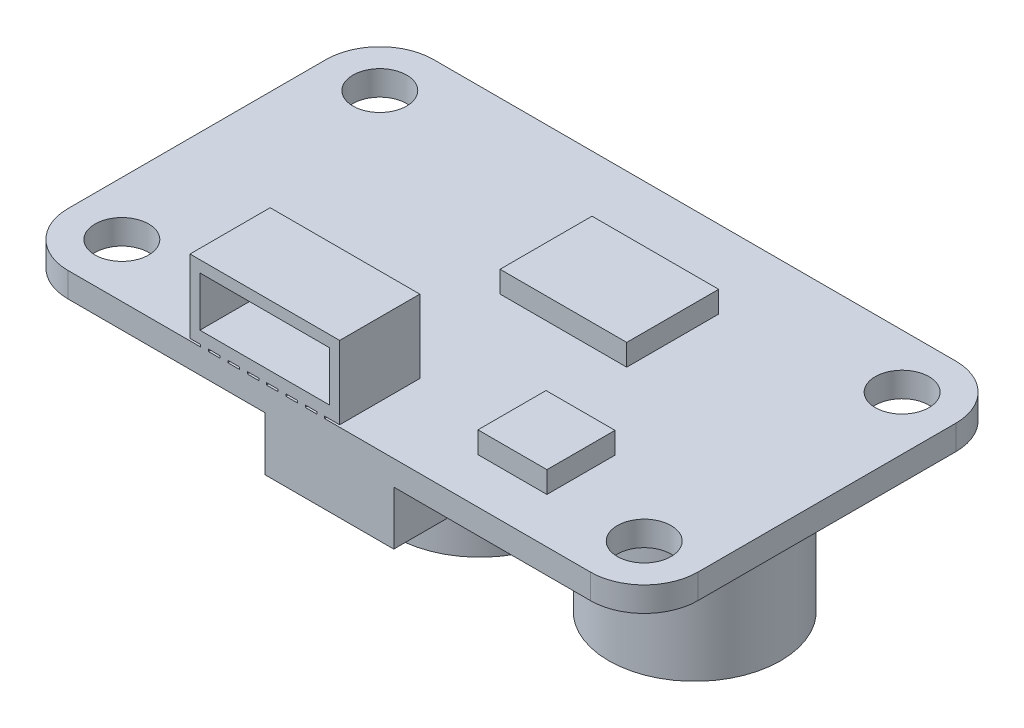
SolidWorks part; units mm, degrees
ref_plane "Front Plane" through (0, 0, 0) normal (0, 0, 1) x (1, 0, 0)
ref_plane "Top Plane" through (0, 0, 0) normal (0, 1, 0) x (1, 0, 0)
ref_plane "Right Plane" through (0, 0, 0) normal (1, 0, 0) x (0, 0, -1)
sketch "Sketch1" plane through (0, 0, 0) normal (0, 1, 0) x (1, 0, 0)
  line L0 (0, 0) -> (0, 8.5) construction
  line L1 (-14.65, 8.5) -> (14.65, 8.5)
  line L2 (-14.65, 8.5) -> (-14.65, -8.5)
  line L3 (-14.65, -8.5) -> (14.65, -8.5)
  line L4 (14.65, 8.5) -> (14.65, -8.5)
  line L5 (-14.65, 8.5) -> (14.65, -8.5) construction
  line L6 (-14.65, -8.5) -> (14.65, 8.5) construction
  line L7 (0, 8.5) -> (0, 0) construction
  line L8 (0, 0) -> (14.65, 0) construction
  circle A0 centre (-12.15, 6) radius 1.25
  circle A1 centre (-12.15, -6) radius 1.25
  circle A2 centre (12.15, -6) radius 1.25
  circle A3 centre (12.15, 6) radius 1.25
  point P0 (0, 0)
  dimension "D7" = 2.5
  dimension "D1" = 29.3
  dimension "D2" = 17
  dimension "D3" = 6
  dimension "D4" = 6
  dimension "D5" = 12.15
  dimension "D6" = 12.15
extrude "Boss-Extrude1" add sketch "Sketch1" along normal blind 1.15
fillet "Fillet1" radius 2.5 4 edges at (-14.65, 0.575, -8.5) (-14.65, 0.575, 8.5) (14.65, 0.575, -8.5) (14.65, 0.575, 8.5)
sketch "Sketch2" plane through (0, 1.15, 0) normal (0, 1, 0) x (1, 0, 0)
  line L0 (-12.15, -8.5) -> (12.15, -8.5) construction
  line L1 (-6.48, -4.7708) -> (0.4823, -4.7708)
  line L2 (-6.48, -4.7708) -> (-6.48, -8.5)
  line L3 (-6.48, -8.5) -> (0.4823, -8.5)
  line L4 (0.4823, -4.7708) -> (0.4823, -8.5)
extrude "Boss-Extrude2" add sketch "Sketch2" along normal blind 3.5
sketch "Sketch3" plane through (0, 0, 8.5) normal (0, 0, 1) x (1, 0, 0)
  line L0 (0.4823, 4.65) -> (0.4823, 1.15) construction
  line L1 (-6.48, 1.15) -> (0.4823, 1.15)
  line L2 (-6.48, 1.15) -> (-6.48, 1.25)
  line L3 (-6.48, 1.25) -> (0.4823, 1.25)
  line L4 (0.4823, 1.15) -> (0.4823, 1.25)
  line L5 (-4.7161, 1.25) -> (-4.7161, 1.15)
  line L6 (-5.9806, 1.25) -> (-5.6161, 1.25)
  line L7 (-5.9806, 1.25) -> (-5.9806, 1.15)
  line L8 (-5.9806, 1.15) -> (-5.6161, 1.15)
  line L9 (-5.6161, 1.25) -> (-5.6161, 1.15)
  line L10 (-5.0806, 1.25) -> (-5.0806, 1.15)
  line L11 (-3.8161, 1.25) -> (-3.8161, 1.15)
  line L12 (-4.1806, 1.25) -> (-4.1806, 1.15)
  line L13 (-2.9161, 1.25) -> (-2.9161, 1.15)
  line L14 (-3.2806, 1.25) -> (-3.2806, 1.15)
  line L15 (-2.0161, 1.25) -> (-2.0161, 1.15)
  line L16 (-2.3806, 1.25) -> (-2.3806, 1.15)
  line L17 (-1.1161, 1.25) -> (-1.1161, 1.15)
  line L18 (-1.4806, 1.25) -> (-1.4806, 1.15)
  line L19 (-0.2161, 1.25) -> (-0.2161, 1.15)
  line L20 (-0.5806, 1.25) -> (-0.5806, 1.15)
  line M7 (0.4823, 1.15) -> (0.4823, 4.65)
  line M9 (-6.48, 4.65) -> (-6.48, 1.15)
  dimension "D1" = 0.1
  dimension "D2" = 7
extrude "Cut-Extrude1" cut sketch "Sketch3" against normal blind 5.5 contours L7 L3 L1 M9 | L10 L3 L9 L1 | L12 L3 L5 L1 | L14 L3 L11 L1 | L16 L3 L13 L1 | L18 L3 L15 L1 | L20 L3 L17 L1 | L3 L19 L1 M7 region at (-6.2303, 1.2, 8.5) region at (-5.3484, 1.2, 8.5) region at (-4.4484, 1.2, 8.5) region at (-3.5484, 1.2, 8.5) region at (-2.6484, 1.2, 8.5) region at (-1.7484, 1.2, 8.5) region at (-0.8484, 1.2, 8.5) region at (0.1331, 1.2, 8.5)
sketch "Sketch4" plane through (0, 0, 8.5) normal (0, 0, 1) x (1, 0, 0)
  line L1 (-6.0186, 4.118) -> (0, 4.118)
  line L2 (-6.0186, 4.118) -> (-6.0186, 1.8112)
  line L3 (-6.0186, 1.8112) -> (0, 1.8112)
  line L4 (0, 4.118) -> (0, 1.8112)
extrude "Cut-Extrude2" cut sketch "Sketch4" against normal blind 3.5
sketch "Sketch5" plane through (0, 1.15, 0) normal (0, 1, 0) x (1, 0, 0)
  line L1 (-1.1534, 4.8757) -> (4.7394, 4.8757)
  line L2 (-1.1534, 4.8757) -> (-1.1534, 0.5977)
  line L3 (-1.1534, 0.5977) -> (4.7394, 0.5977)
  line L4 (4.7394, 4.8757) -> (4.7394, 0.5977)
extrude "Boss-Extrude3" add sketch "Sketch5" along normal blind 1
sketch "Sketch6" plane through (0, 1.15, 0) normal (0, 1, 0) x (1, 0, 0)
  line L1 (4.8023, -3.219) -> (8.0108, -3.219)
  line L2 (4.8023, -3.219) -> (4.8023, -6.3856)
  line L3 (4.8023, -6.3856) -> (8.0108, -6.3856)
  line L4 (8.0108, -3.219) -> (8.0108, -6.3856)
extrude "Boss-Extrude4" add sketch "Sketch6" along normal blind 1
sketch "Sketch7" plane through (0, 0, 0) normal (0, -1, 0) x (1, 0, 0)
  line L0 (0, 8.5) -> (0, -8.5) construction
  line L1 (-12.15, 8.5) -> (12.15, 8.5) construction
  line L2 (12.15, -8.5) -> (-12.15, -8.5) construction
  line L4 (-3, 2.5) -> (3, 2.5)
  line L5 (-3, 2.5) -> (-3, 8.5)
  line L6 (-3, 8.5) -> (3, 8.5)
  line L7 (3, 2.5) -> (3, 8.5)
  line L8 (-3, 2.5) -> (3, 8.5) construction
  line L9 (-3, 8.5) -> (3, 2.5) construction
  point P6 (0, 5.5)
  dimension "D1" = 6
  dimension "D2" = 6
extrude "Boss-Extrude5" add sketch "Sketch7" along normal blind 3
sketch "Sketch8" plane through (0, -3, 0) normal (0, -1, 0) x (1, 0, 0)
  line L4 (3, 2.5) -> (3, 8.5)
  line L5 (3, 8.5) -> (-3, 8.5)
  line L6 (-3, 8.5) -> (-3, 2.5)
  line L7 (-3, 2.5) -> (3, 2.5)
  line L8 (3, 2.5) -> (3, 8.5)
  line L9 (3, 8.5) -> (-3, 8.5)
  line L10 (-3, 8.5) -> (-3, 2.5)
  line L11 (-3, 2.5) -> (3, 2.5)
  circle A0 centre (0, 5.5677) radius 1.858
  circle A1 centre (0, 5.5677) radius 0.6038
  line M5 (3, 2.5) -> (3, 8.5)
  line M6 (3, 8.5) -> (-3, 8.5)
  line M7 (-3, 8.5) -> (-3, 2.5)
  line M8 (-3, 2.5) -> (3, 2.5)
  dimension "D1" = 0
extrude "Cut-Extrude3" cut sketch "Sketch8" against normal blind 0.5 contours A0 M8 M5 M6 M7 | A1 region at (0, -3, 2.5849) region at (0, -3, 5.5677)
sketch "Sketch10" plane through (0, 0, 0) normal (0, -1, 0) x (1, 0, 0)
  line L0 (0, -3.5) -> (9, -3.5) construction
  line L1 (5, 0.5) -> (5, -8.5) construction
  line L2 (12.15, -8.5) -> (-12.15, -8.5) construction
  circle A0 centre (5, -3.5) radius 4
  circle A1 centre (-5, -3.5) radius 4
  dimension "D2" = 8
  dimension "D1" = 9
  dimension "D3" = 5
  dimension "D4" = 9
extrude "Boss-Extrude6" add sketch "Sketch10" along normal blind 10
sketch "Sketch11" plane through (0, -10, 0) normal (0, -1, 0) x (1, 0, 0)
  circle A0 centre (-5, -3.5) radius 2.5
  circle A1 centre (5, -3.5) radius 2.5
  dimension "D1" = 5
  dimension "D2" = 5
extrude "Cut-Extrude4" cut sketch "Sketch11" against normal blind 2
sketch "Sketch12" plane through (0, -8, 0) normal (0, -1, 0) x (1, 0, 0)
  circle A1 centre (-5, -3.5) radius 2.5 construction
  circle A2 centre (-5, -3.5) radius 2.4
  circle A3 centre (-5, -3.5) radius 2.4
  circle A4 centre (-5, -3.5) radius 2.5
  dimension "D1" = 0.1
extrude "Cut-Extrude5" cut sketch "Sketch12" against normal blind 2
fillet "Fillet2" radius 2 1 edges at (-5, -8, -5.9)
sketch "Sketch13" plane through (0, -8, 0) normal (0, -1, 0) x (1, 0, 0)
  circle A0 centre (5, -3.5) radius 2.4
  circle A1 centre (5, -3.5) radius 2.5
  circle A2 centre (5, -3.5) radius 2.5
  dimension "D1" = 0
  dimension "D2" = 0.1
extrude "Cut-Extrude6" cut sketch "Sketch13" against normal blind 2
fillet "Fillet3" radius 2 1 edges at (5, -8, -5.9)
chamfer "Chamfer1" distance 0.5 angle 45 2 edges at (-5, 0, 0.5) (5, 0, 0.5)
sketch "Sketch14" plane through (0, -10, 0) normal (0, -1, 0) x (1, 0, 0)
  circle A1 centre (-5, -3.5) radius 3.6
  circle A2 centre (-5, -3.5) radius 3.5
  circle A3 centre (-5, -3.5) radius 3.5
  circle A4 centre (5, -3.5) radius 3.5
  circle A5 centre (5, -3.5) radius 3.6
  dimension "D1" = 0.5
  dimension "D2" = 0.1
extrude "Cut-Extrude7" cut sketch "Sketch14" against normal blind 2
